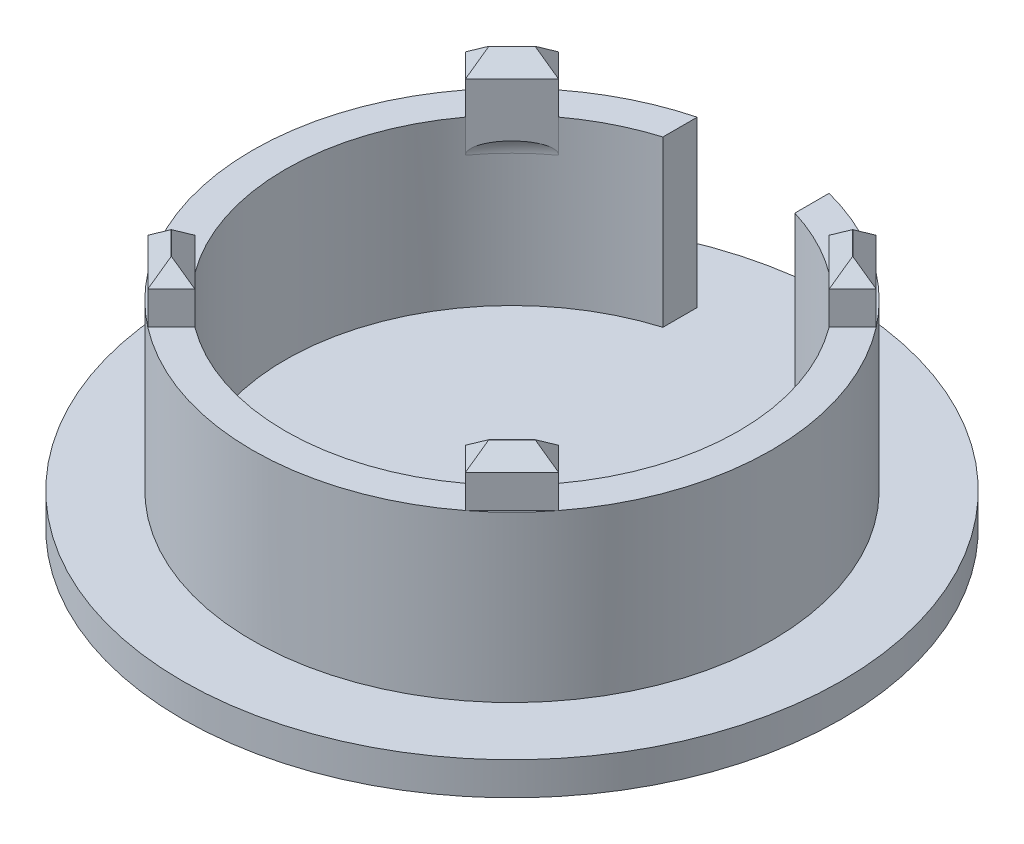
SolidWorks part; units mm, degrees
ref_plane "Front Plane" through (0, 0, 0) normal (0, 0, 1) x (1, 0, 0)
ref_plane "Top Plane" through (0, 0, 0) normal (0, 1, 0) x (1, 0, 0)
ref_plane "Right Plane" through (0, 0, 0) normal (1, 0, 0) x (0, 0, -1)
sketch "Sketch1" plane through (0, 0, 0) normal (0, 1, 0) x (1, 0, 0)
  circle A0 centre (0, 0) radius 20.0025
  circle A1 centre (0, 0) radius 17.4625
  dimension "D1" = 2.54
  dimension "D2" = 40.005
extrude "Boss-Extrude1" add sketch "Sketch1" along normal blind 12.7
sketch "Sketch2" plane through (0, 12.7, 0) normal (0, 1, 0) x (1, 0, 0)
  line L0 (0, 0) -> (0, 14.5853) construction
  line L1 (-14.0126, 10.4205) -> (-10.4205, 14.0126)
  line L2 (8.9883, 0) -> (0, 0) construction
  line L3 (0, 0) -> (-15.4538, 15.4538) construction
  line L4 (-14.0126, 10.4205) -> (-15.8255, 12.2334)
  line L5 (-10.4205, 14.0126) -> (-12.2334, 15.8255)
  line L6 (-15.8255, 12.2334) -> (-12.2334, 15.8255)
  line L7 (15.8255, 12.2334) -> (12.2334, 15.8255)
  line L8 (10.4205, 14.0126) -> (12.2334, 15.8255)
  line L9 (14.0126, 10.4205) -> (15.8255, 12.2334)
  line L10 (14.0126, 10.4205) -> (10.4205, 14.0126)
  line L11 (14.0126, -10.4205) -> (15.8255, -12.2334)
  line L12 (14.0126, -10.4205) -> (10.4205, -14.0126)
  line L13 (10.4205, -14.0126) -> (12.2334, -15.8255)
  line L14 (15.8255, -12.2334) -> (12.2334, -15.8255)
  line L15 (-10.4205, -14.0126) -> (-12.2334, -15.8255)
  line L16 (-15.8255, -12.2334) -> (-12.2334, -15.8255)
  line L17 (-14.0126, -10.4205) -> (-15.8255, -12.2334)
  line L18 (-14.0126, -10.4205) -> (-10.4205, -14.0126)
  circle A0 centre (0, 0) radius 17.4625 construction
  circle A1 centre (0, 0) radius 20.0025
  circle A2 centre (0, 0) radius 20.0025 construction
  arc A3 (-14.0126, 10.4205) -> (-12.3479, 12.3479) centre (0, 0) ccw construction
  point P7 (-14.0294, 14.0294)
  dimension "D2" = 45
  dimension "D3" = 5.08
  dimension "D1" = 0
extrude "Boss-Extrude2" add sketch "Sketch2" along normal blind 3.81
fillet "Fillet1" radius 2.54 4 edges at (12.3479, 12.7, -12.3479) (12.3479, 12.7, 12.3479) (-12.3479, 12.7, 12.3479) (-12.3479, 12.7, -12.3479)
sketch "Sketch3" plane through (0, 12.7, 0) normal (0, 1, 0) x (1, 0, 0)
  line L1 (-5.08, 20.0025) -> (5.08, 20.0025)
  line L2 (-5.08, 20.0025) -> (-5.08, 14.9225)
  line L3 (-5.08, 14.9225) -> (5.08, 14.9225)
  line L4 (5.08, 20.0025) -> (5.08, 14.9225)
  line L5 (-5.08, 20.0025) -> (5.08, 14.9225) construction
  line L6 (-5.08, 14.9225) -> (5.08, 20.0025) construction
  arc A0 (10.4205, 14.0126) -> (-10.4205, 14.0126) centre (0, 0) ccw construction
  arc A1 (12.2334, 15.8255) -> (-12.2334, 15.8255) centre (0, 0) ccw construction
  point P0 (0, 17.4625)
  dimension "D1" = 10.16
extrude "Cut-Extrude1" cut sketch "Sketch3" against normal up to next
sketch "Sketch5" plane through (0, 0, 0) normal (0, -1, 0) x (1, 0, 0)
  circle A0 centre (0, 0) radius 25.4
  dimension "D1" = 50.8
extrude "Boss-Extrude3" add sketch "Sketch5" along normal blind 2.54
chamfer "Chamfer1" distance 1.27 angle 45 16 edges at (12.2165, 16.51, -12.2165) (11.3269, 16.51, -14.919) (14.0294, 16.51, -14.0294) (14.919, 16.51, -11.3269) (14.919, 16.51, 11.3269) (14.0294, 16.51, 14.0294) (11.3269, 16.51, 14.919) (12.2165, 16.51, 12.2165) (-11.3269, 16.51, 14.919) (-14.0294, 16.51, 14.0294) (-14.919, 16.51, 11.3269) (-12.2165, 16.51, 12.2165) (-14.0294, 16.51, -14.0294) (-11.3269, 16.51, -14.919) (-12.2165, 16.51, -12.2165) (-14.919, 16.51, -11.3269)
sketch "Sketch6" plane through (0, -2.54, 0) normal (0, -1, 0) x (1, 0, 0)
  line L0 (-34.5485, 0) -> (33.2867, 0) construction
  line L1 (-34.3338, -3.175) -> (33.072, -3.175) construction
  text T0 "CrabWorks" font "DINOT-BoldItalic" height 6.35
  dimension "D1" = 3.175
extrude "Cut-Extrude2" cut sketch "Sketch6" against normal blind 0.635
